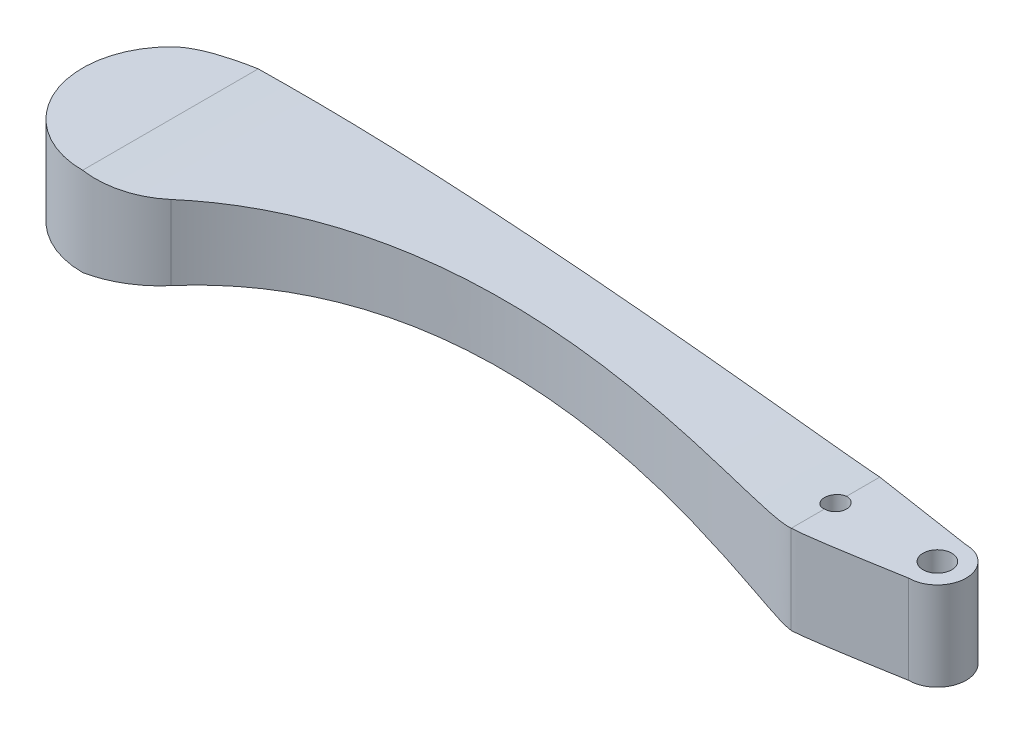
SolidWorks part; units mm, degrees
ref_plane "Front Plane" through (0, 0, 0) normal (0, 0, 1) x (1, 0, 0)
ref_plane "Top Plane" through (0, 0, 0) normal (0, 1, 0) x (1, 0, 0)
ref_plane "Right Plane" through (0, 0, 0) normal (1, 0, 0) x (0, 0, -1)
sketch "Sketch1" plane through (0, 0, 0) normal (0, 1, 0) x (1, 0, 0)
  line L0 (0, 0) -> (-300, 0) construction
  line L1 (0, 0) -> (46, 0) construction
  line L2 (-300, 0) -> (-300, 40) construction
  line L3 (-328.2843, 28.2843) -> (-271.7157, -28.2843) construction
  circle A0 centre (0, 0) radius 5
  circle A1 centre (46, 0) radius 6.5
  circle A2 centre (-300, 0) radius 40
  circle A3 centre (0, 0) radius 20
  circle A4 centre (46, 0) radius 13
  spline S0 degree 3 poles (-271.7157, -28.2843) (-189.2199, 54.2115) (-20, -20) (0, -20) knots 0 0 0 0 1 1 1 1
  spline S1 degree 3 poles (-328.2843, 28.2843) (-300, 56.5685) (-114.8731, 40.3783) (0, 20) knots 0 0 0 0 1 1 1 1
  spline S2 degree 2 poles (0, -20) (5.9085, -20) (46, -13) knots 0 0 0 1 1 1
  spline S3 degree 2 poles (0, 20) (0.0315, 20) (46, 13) knots 0 0 0 1 1 1
  dimension "D3" = 10
  dimension "D4" = 13
  dimension "D5" = 80
  dimension "D6" = 40
  dimension "D7" = 45
  dimension "D8" = 120
  dimension "D9" = 350
  dimension "D10" = 350
  dimension "D11" = 60
  dimension "D12" = 26
  dimension "D1" = 46
  dimension "D2" = 300
extrude "Boss-Extrude1" add sketch "Sketch1" along normal blind 20 and the other way blind 20 contours S1 A2 | S1 A2 S0 A3 | S3 A3 S0 A0 | S3 A3 S2 A4 | A4 A1 region at (-299.9271, 0, 0.2395) region at (-151.7179, 0, -19.1123) region at (-19.1932, 0, -3.0516) region at (26.0397, 0, 0.3418) region at (54.9324, 0, -8.9324)
sketch "Sketch3" plane through (0, 0, 0) normal (0, 0, 1) x (1, 0, 0)
  line L0 (0, 174.4861) -> (0, -69.6609) construction
  line L1 (-300, 0) -> (0, 0) construction
  line L2 (-300, -20) -> (0, -20)
  line L6 (-300, -20) -> (-300, 20)
  line L7 (-340, -20) -> (-271.7157, -20) construction
  line L8 (-271.7157, 20) -> (-340, 20) construction
  line L9 (-300, 20) -> (0, 20)
  spline S0 degree 3 poles (-300, 20) (-244.1119, 10.6387) (-66.2761, 12.7946) (0, 20) knots 0 0 0 0 1 1 1 1
  spline S1 degree 3 poles (-300, -20) (-244.1119, -10.6387) (-66.2761, -12.7946) (0, -20) knots 0 0 0 0 1 1 1 1
  dimension "D3" = 200
  dimension "D1" = 300
  dimension "D2" = 170
extrude "Cut-Extrude2" cut sketch "Sketch3" against normal blind 50 and the other way blind 50 contours S1 L2 | L9 S0 region at (-155.4339, -17.4337, 0)
